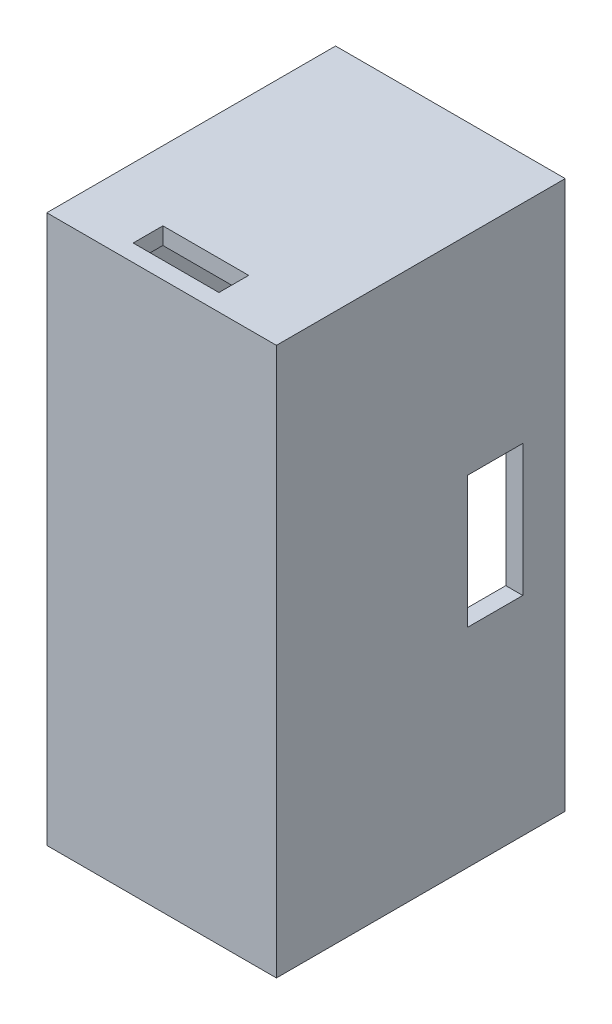
SolidWorks part; units mm, degrees
ref_plane "Front Plane" through (0, 0, 0) normal (0, 0, 1) x (1, 0, 0)
ref_plane "Top Plane" through (0, 0, 0) normal (0, 1, 0) x (1, 0, 0)
ref_plane "Right Plane" through (0, 0, 0) normal (1, 0, 0) x (0, 0, -1)
sketch "Sketch1" plane through (0, 0, 0) normal (0, 0, 1) x (1, 0, 0)
  line L0 (-11.2217, -8.2927) -> (-6.2783, -8.2927)
  line L1 (-9.25, 44.3338) -> (9.25, 44.3338)
  line L2 (-9.25, 44.3338) -> (-9.25, 21.3338)
  line L3 (-9.25, 21.3338) -> (9.25, 21.3338)
  line L4 (9.25, 44.3338) -> (9.25, 21.3338)
  line L5 (-13.5173, 46.3338) -> (13.5173, 46.3338)
  line L6 (-13.5173, 46.3338) -> (-13.5173, -18.169)
  line L7 (-13.5173, -18.169) -> (13.5173, -18.169)
  line L8 (13.5173, 46.3338) -> (13.5173, -18.169)
  line L9 (-8.75, 13.8323) -> (-13.5173, 13.8323) construction
  line L10 (8.75, 13.8323) -> (13.5173, 13.8323) construction
  circle A0 centre (-8.75, 13.8323) radius 0.75
  circle A1 centre (8.75, 13.8323) radius 0.75
  circle A2 centre (-8.75, -8.6677) radius 0.75
  circle A3 centre (8.75, -8.6677) radius 0.75
  circle A4 centre (-8.75, 13.8323) radius 2.5
  circle A5 centre (8.75, 13.8323) radius 2.5
  circle A6 centre (8.75, -8.6677) radius 2.5
  circle A7 centre (-8.75, -8.6677) radius 2.5
  point P4 (0, 21.3338)
  point P21 (0, -18.169)
  dimension "D3" = 1.5
  dimension "D6" = 5
  dimension "D1" = 18.5
  dimension "D2" = 23
  dimension "D4" = 17.5
  dimension "D5" = 22.5
  dimension "D7" = 0.375
  dimension "D8" = 2
extrude "Boss-Extrude2" add sketch "Sketch1<3>" along normal blind 2 contours L6 L7 L8 L5
sketch "Sketch1<3>" plane through (0, 0, 0) normal (0, 0, 1) x (1, 0, 0) same geometry as "Sketch1"
extrude "Boss-Extrude3" add sketch "Sketch1<4>" against normal blind 3 contours L8 L5 L6 L7 A7 A6 A5 A4 L1 L4 L3 L2 | A5 A1 | A1 | A4 A0 | A0 | L0 A7 A2 | L0 A2 | L0 A7 A2 | L0 A2 | A6 A3 | A3 region at (-8.75, -7.3678, 0) region at (-8.75, -9.6308, 0) region at (-8.75, -8.139, 0) region at (-8.75, -8.7962, 0) region at (0, 8.3753, 0) region at (-8.75, 13.8323, 0) region at (8.75, 13.8323, 0) region at (8.75, -8.6677, 0) region at (-11.1793, 13.8323, 0) region at (6.3207, 13.8323, 0) region at (6.3207, -8.6677, 0)
sketch "Sketch1<4>" plane through (0, 0, 0) normal (0, 0, 1) x (1, 0, 0) same geometry as "Sketch1"
extrude "Boss-Extrude6" add sketch "Sketch1" against normal offset from surface (12 mm away) 9 contours A4 A0 | L0 A7 A2 | A6 A3 | A5 A1 region at (-8.75, -9.6308, 0) region at (-11.1793, 13.8323, 0) region at (6.3207, 13.8323, 0) region at (6.3207, -8.6677, 0) up to face at (0, 14.0824, -3) offset beyond the face yes
sketch "Sketch2" plane through (0, 0, -3) normal (0, 0, -1) x (-1, 0, 0)
  line L9 (9.25, 44.3338) -> (-9.25, 44.3338) construction
  line L10 (5.35, 44.3338) -> (-4.75, 44.3338)
  line L11 (5.35, 44.3338) -> (5.35, 49.9441)
  line L12 (5.35, 49.9441) -> (-4.75, 49.9441)
  line L13 (-4.75, 44.3338) -> (-4.75, 49.9441)
  line L14 (-9.25, 44.3338) -> (-9.25, 21.3338) construction
  line L16 (-4.75, 44.3338) -> (5.35, 44.3338)
  line L17 (-4.75, 44.3338) -> (-4.75, 37.3338)
  line L18 (-4.75, 37.3338) -> (5.35, 37.3338)
  line L19 (5.35, 44.3338) -> (5.35, 37.3338)
  dimension "D1" = 4.5
  dimension "D2" = 3.9
  dimension "D3" = 7
extrude "Cut-Extrude1" cut sketch "Sketch2" along normal blind 3.5 from surface contours L17 L18 L19 L16 | L10 L11 L12 L13 starting at face at (0, 32.8338, 0)
sketch "Sketch4" plane through (9.25, 0, 0) normal (-1, 0, 0) x (0, 0, 1)
  line L0 (-3, 21.3338) -> (0, 21.3338) construction
  line L1 (-3, 21.3338) -> (0, 21.3338)
  line L2 (-3, 21.3338) -> (-3, 22.3338)
  line L3 (-3, 46.3338) -> (-3, -18.169) construction
  line L4 (-3, 22.3338) -> (-4, 21.3338)
  line L5 (-4, 21.3338) -> (-4, 20.631)
  line L6 (-4, 20.631) -> (-3, 20.267)
  line L7 (-3, 20.267) -> (-3, 21.3338)
  line L8 (-3, 22.3338) -> (-2.4226, 21.3338)
  line M8 (-3, 44.3338) -> (-3, 21.3338)
  line M9 (-3, 21.3338) -> (0, 21.3338)
  dimension "D1" = 1
  dimension "D2" = 1
  dimension "D3" = 110
  dimension "D4" = 60
extrude "Boss-Extrude7" add sketch "Sketch4" along normal up to surface (18.5 mm away) contours L8 M8 M9 | L6 L7 L4 L5 M8 region at (9.25, 21.6672, -2.8075) region at (9.25, 21.1675, -3.4179) up to face at (-9.25, 32.8338, -1.5)
sketch "Sketch5" plane through (0, 0, -3) normal (0, 0, -1) x (-1, 0, 0)
  line L0 (13.5173, 46.3338) -> (13.5173, -18.169) construction
  line L1 (-13.5173, 46.3338) -> (13.5173, 46.3338)
  line L2 (-13.5173, 46.3338) -> (-13.5173, 44.3338)
  line L3 (-13.5173, 44.3338) -> (13.5173, 44.3338)
  line L4 (13.5173, 46.3338) -> (13.5173, 44.3338)
  line L5 (9.25, 44.3338) -> (5.35, 44.3338) construction
  line L6 (13.5173, -18.169) -> (-13.5173, -18.169) construction
  line L7 (-13.5173, 44.3338) -> (-11.5173, 44.3338)
  line L8 (-13.5173, 44.3338) -> (-13.5173, -18.169)
  line L9 (-13.5173, -18.169) -> (-11.5173, -18.169)
  line L10 (-11.5173, 44.3338) -> (-11.5173, -18.169)
  line L12 (13.5173, 44.3338) -> (11.5173, 44.3338)
  line L13 (13.5173, 44.3338) -> (13.5173, -18.169)
  line L14 (13.5173, -18.169) -> (11.5173, -18.169)
  line L15 (11.5173, 44.3338) -> (11.5173, -18.169)
  line L16 (-11.5173, -18.169) -> (11.5173, -18.169)
  line L17 (-11.5173, -18.169) -> (-11.5173, -15.169)
  line L18 (-11.5173, -15.169) -> (11.5173, -15.169)
  line L19 (11.5173, -18.169) -> (11.5173, -15.169)
  line M19 (-9.25, 44.3338) -> (-4.75, 44.3338)
  line M20 (-4.75, 44.3338) -> (-4.75, 46.3338)
  line M21 (-4.75, 46.3338) -> (-13.5173, 46.3338)
  line M22 (-13.5173, 46.3338) -> (-13.5173, -18.169)
  line M23 (-13.5173, -18.169) -> (13.5173, -18.169)
  line M24 (13.5173, -18.169) -> (13.5173, 46.3338)
  line M25 (13.5173, 46.3338) -> (5.35, 46.3338)
  line M26 (5.35, 46.3338) -> (5.35, 44.3338)
  line M27 (5.35, 44.3338) -> (9.25, 44.3338)
  dimension "D1" = 2
  dimension "D2" = 2
extrude "Boss-Extrude9" add sketch "Sketch5" along normal offset from surface (29 mm away) 20 contours L3 M22 M19 M20 M21 | L10 L3 M22 M23 | L3 L1 M20 M26 | L3 M27 M24 M25 M26 | L3 L15 M23 M24 | L18 L10 L15 M23 region at (9.1337, 45.3338, -3) region at (-0.3, 45.3338, -3) region at (12.5173, 13.0824, -3) region at (-9.4337, 45.3338, -3) region at (0, -16.669, -3) region at (-12.5173, 13.0824, -3) up to face at (11.25, 13.8323, -12) offset beyond the face yes
sketch "Sketch6" plane through (0, -15.169, 0) normal (0, 1, 0) x (1, 0, 0)
  line L1 (-11.5173, 31.5) -> (11.5173, 31.5)
  line L2 (-11.5173, 31.5) -> (-11.5173, 30.5)
  line L3 (-11.5173, 30.5) -> (11.5173, 30.5)
  line L4 (11.5173, 32) -> (-11.5173, 32)
  line L5 (-11.5173, 32) -> (-11.5173, 3)
  line L6 (-11.5173, 3) -> (11.5173, 3)
  line L7 (11.5173, 3) -> (11.5173, 32)
  line L8 (11.5173, 32) -> (-11.5173, 32)
  line L9 (-11.5173, 32) -> (-11.5173, 3)
  line L10 (-11.5173, 3) -> (11.5173, 3)
  line L11 (11.5173, 3) -> (11.5173, 32)
  line L12 (11.5173, 31.5) -> (11.5173, 30.5)
  dimension "D2" = 1
  dimension "D3" = 0.5
  dimension "D1" = 0
extrude "Cut-Extrude2" cut sketch "Sketch6" against normal blind 0.5 contours L3 L12 L1 L2
sketch "Sketch8" plane through (0, -18.169, 0) normal (0, -1, 0) x (1, 0, 0)
  line L0 (-13.5173, -32) -> (13.5173, -32) construction
  line L1 (-7.35, -19.9) -> (7.35, -19.9)
  line L2 (-7.35, -19.9) -> (-7.35, -28)
  line L3 (-7.35, -28) -> (7.35, -28)
  line L4 (7.35, -19.9) -> (7.35, -28)
  line L5 (0, -32) -> (0, -28) construction
  dimension "D1" = 14.7
  dimension "D2" = 8.1
  dimension "D3" = 4
extrude "Cut-Extrude3" cut sketch "Sketch8" against normal up to next contours L1 L4 L3 L2
sketch "Sketch9" plane through (13.5173, 0, 0) normal (1, 0, 0) x (0, 0, -1)
  line L0 (-2, 46.3338) -> (-2, -18.169) construction
  line L1 (20.5, 21.8324) -> (27, 21.8324)
  line L2 (20.5, 21.8324) -> (20.5, 6.3324)
  line L3 (20.5, 6.3324) -> (27, 6.3324)
  line L4 (27, 21.8324) -> (27, 6.3324)
  line L5 (-2, 14.0824) -> (20.5, 14.0824) construction
  line L6 (32, -18.169) -> (32, 46.3338) construction
  dimension "D1" = 6.5
  dimension "D2" = 15.5
  dimension "D3" = 5
extrude "Cut-Extrude4" cut sketch "Sketch9" against normal up to next
sketch "Sketch11" plane through (0, 0, -3) normal (0, 0, 1) x (1, 0, 0)
  line L4 (4.75, 44.3338) -> (4.75, 46.3338)
  line L5 (4.75, 46.3338) -> (-5.35, 46.3338)
  line L6 (-5.35, 46.3338) -> (-5.35, 44.3338)
  line L7 (-5.35, 44.3338) -> (4.75, 44.3338)
  line L8 (4.75, 44.3338) -> (4.75, 46.3338)
  line L9 (4.75, 46.3338) -> (-5.35, 46.3338)
  line L10 (-5.35, 46.3338) -> (-5.35, 44.3338)
  line L11 (-5.35, 44.3338) -> (4.75, 44.3338)
  dimension "D1" = 0
extrude "Cut-Extrude5" cut sketch "Sketch11" against normal blind 0.5
